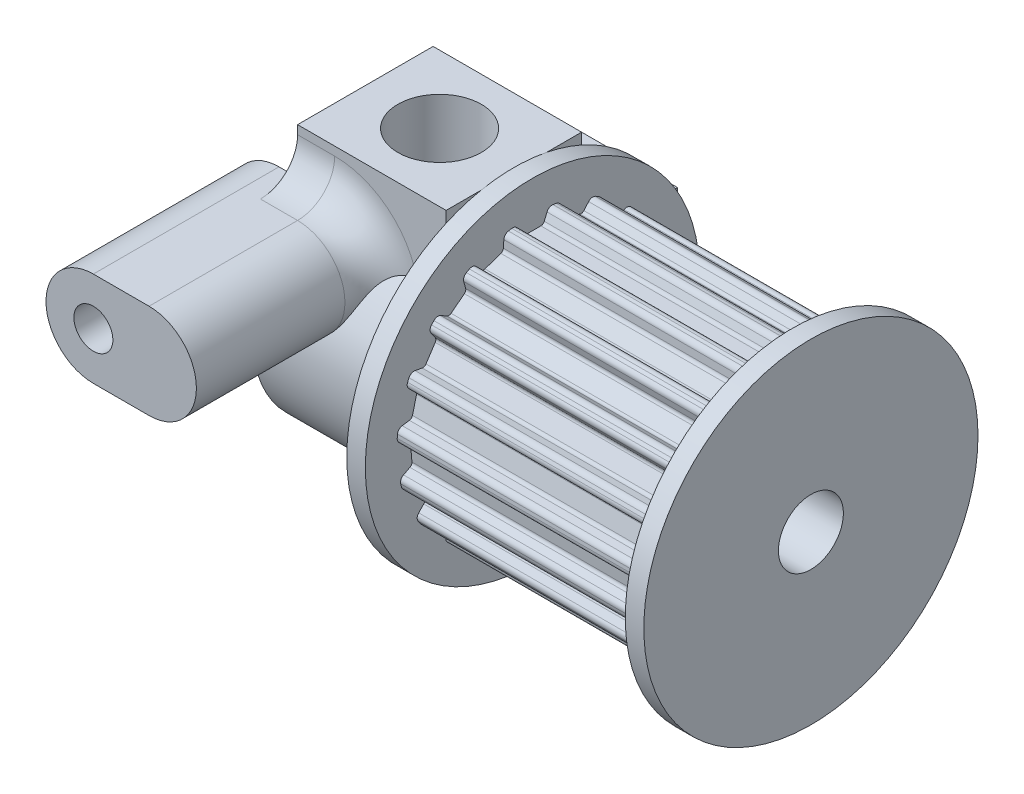
SolidWorks part; units mm, degrees
material "PLA Black"
ref_plane "Front" through (0, 0, 0) normal (0, 0, 1) x (1, 0, 0)
ref_plane "Top" through (0, 0, 0) normal (0, 1, 0) x (1, 0, 0)
ref_plane "Right" through (0, 0, 0) normal (1, 0, 0) x (0, 0, -1)
sketch "Sketch1" plane through (0, 0, 0) normal (1, 0, 0) x (0, 0, -1)
  line L0 (1.118, 1) -> (-1.118, 1) construction
  line L1 (-3.65, 4.8249) -> (3.65, 4.8249)
  line L2 (4.8249, 3.65) -> (4.8249, -3.65)
  line L3 (0, 0) -> (11.6334, 0) construction
  line L4 (0, 0) -> (0, 8.6732) construction
  arc A0 (-1.118, 1) -> (1.118, 1) centre (0, 0) ccw construction
  circle A1 centre (0, 0) radius 1.75
  arc A2 (4.8249, -3.65) -> (-3.65, 4.8249) centre (0, 0) cw
  arc A3 (4.8249, 3.65) -> (3.65, 4.8249) centre (0, 0) ccw
  dimension "D1" = 3
  dimension "D3" = 0.25
  dimension "D5" = 6.05
  dimension "D2" = 1
  dimension "D4" = 7.3
extrude "Boss-Extrude1" add sketch "Sketch1" along normal mid plane 8
sketch "Sketch2" plane through (0, 4.8249, 0) normal (0, 1, 0) x (1, 0, 0)
  circle A0 centre (0, 0) radius 2.25
  dimension "D1" = 4.5
extrude "Cut-Extrude1" cut sketch "Sketch2" against normal blind 5
sketch "Sketch7" plane through (4, 0, 0) normal (1, 0, 0) x (0, 0, -1)
  circle A0 centre (0, 0) radius 1.75 construction
  circle A1 centre (0, 0) radius 7.3
  circle A2 centre (0, 0) radius 1.75
  dimension "D1" = 14.6
extrude "Boss-Extrude5" add sketch "Sketch7" along normal blind 15
sketch "Sketch8" plane through (19, 0, 0) normal (1, 0, 0) x (0, 0, -1)
  line L0 (-0.4541, 6.5499) -> (0.4528, 6.5499)
  line L1 (0.6374, 6.6734) -> (0.7865, 7.0333)
  line L2 (-0.6389, 6.6734) -> (-0.788, 7.0333)
  line L6 (0, 9.2013) -> (0, 0) construction
  arc A0 (0.4528, 6.5499) -> (0.6374, 6.6734) centre (0.4526, 6.7499) ccw
  arc A1 (-0.4541, 6.5499) -> (-0.6389, 6.6734) centre (-0.4541, 6.7499) cw
  arc A2 (0.7865, 7.0333) -> (1.1093, 7.2152) centre (1.0638, 6.9187) cw
  arc A3 (-0.788, 7.0333) -> (-1.1108, 7.215) centre (-1.0652, 6.9185) ccw
  circle A4 centre (0, 0) radius 7.3 construction
  arc A5 (-1.1108, 7.215) -> (1.1093, 7.2152) centre (0, 0) cw
  point P3 (-0.0007, 6.5499)
  point P15 (0, 9.84)
extrude "Cut-Extrude3" cut sketch "Sketch8" against normal up to surface (15 mm away) up to face at (4, 0, -7.3)
pattern_circular "CirPattern1" count 19 over 360 about axis through (19, 0, 0) along (-1, 0, 0) of "Cut-Extrude3"
sketch "Sketch9" plane through (19, 0, 0) normal (1, 0, 0) x (0, 0, -1)
  circle A0 centre (0, 0) radius 9
  circle A1 centre (0, 0) radius 1.75 construction
  circle A2 centre (0, 0) radius 1.75
  dimension "D1" = 18
extrude "Boss-Extrude6" add sketch "Sketch9" along normal blind 1
sketch "Sketch10" plane through (4, 0, 0) normal (-1, 0, 0) x (0, 0, 1)
  circle A0 centre (0, 0) radius 9
  circle A1 centre (0, 0) radius 9 construction
  circle A2 centre (0, 0) radius 1.75 construction
  circle A3 centre (0, 0) radius 1.75
extrude "Boss-Extrude7" add sketch "Sketch10" against normal blind 1
sketch "Sketch3" plane through (0, 0, -4.8249) normal (0, 0, -1) x (-1, 0, 0)
  circle A0 centre (0, 0) radius 2.25
  dimension "D1" = 4.5
extrude "Cut-Extrude2" cut sketch "Sketch3" against normal blind 5
sketch "Sketch4" plane through (0, 4.8249, 0) normal (0, 1, 0) x (1, 0, 0)
  line L0 (4, 3.65) -> (-4, 3.65) construction
  line L2 (4, -3.65) -> (-4, -3.65) construction
  line L3 (-4, 3.65) -> (-4, -3.65) construction
  line L4 (4, 3.65) -> (-4, 3.65)
  line L5 (4, 3.65) -> (4, -3.65)
  line L6 (4, -3.65) -> (-4, -3.65)
  line L7 (-4, 3.65) -> (-4, -3.65)
  line L8 (4, 7.3) -> (4, -7.3) construction
  circle A0 centre (0, 0) radius 2.25 construction
  circle A1 centre (0, 0) radius 2.25
extrude "Boss-Extrude2" add sketch "Sketch4" along normal blind 4
sketch "Sketch5" plane through (0, 0, -4.8249) normal (0, 0, -1) x (-1, 0, 0)
  line L0 (-4, 3.65) -> (4, 3.65) construction
  line L1 (4, -3.65) -> (4, 3.65) construction
  line L2 (-4, -3.65) -> (4, -3.65) construction
  line L4 (-4, 3.65) -> (4, 3.65)
  line L5 (4, -3.65) -> (4, 3.65)
  line L6 (-4, -3.65) -> (4, -3.65)
  line L7 (-4, -3.65) -> (-4, 3.65)
  line L8 (-4, -7.3) -> (-4, 7.3) construction
  circle A0 centre (0, 0) radius 2.25 construction
  circle A1 centre (0, 0) radius 2.25
extrude "Boss-Extrude3" add sketch "Sketch5" along normal blind 4
ref_axis "Axis1" through (20, 0, 0) along (-1, 0, 0)
sketch "Sketch6" plane through (0, 0, 3.65) normal (0, 0, 1) x (1, 0, 0)
  line L0 (-4, 8.8249) -> (-4, 4.8249) construction
  line L2 (-2, 6.3555) -> (-5, 6.3555)
  line L3 (-5, 1.2545) -> (-2, 1.2545)
  line L6 (20, 0) -> (-4, 0) construction
  circle A0 centre (-5, 3.805) radius 1.0505
  arc A1 (-5, 6.3555) -> (-5, 1.2545) centre (-5, 3.805) ccw
  arc A2 (-2, 6.3555) -> (-2, 1.2545) centre (-2, 3.805) cw
  dimension "D1" = 2.101
  dimension "D2" = 3.805
  dimension "D3" = 1.5
  dimension "D4" = 1
  dimension "D5" = 3
extrude "Boss-Extrude4" add sketch "Sketch6" along normal blind 10
fillet "Fillet1" radius 2 2 edges at (-0.6029, 5.9388, 3.65) (-3, 6.3555, 3.65)
equation "\"knee_angle\"= 70"
equation "\"ankle_angle\" = 70"
equation "\"hip_angle\" = 30"
equation "\"spring_ankle_parallel_arm_diameter\"= 1.5"
equation "\"spring_ankle_parallel_arm_length\"= 13"
equation "\"spring_ankle_parallel_intern_diameter\"= 5.7"
equation "\"spring_ankle_parallel_angle\"= \"ankle_angle\""
equation "\"spring_ankle_parallel_turns\"= 3"
equation "\"spring_ankle_parallel_pitch\"= \"spring_ankle_parallel_arm_diameter\" * 1.01"
equation "\"spring_ankle_parallel_cutting_distance\"= (1-\"spring_ankle_parallel_angle\" / 360) * \"spring_ankle_parallel_pitch\""
equation "\"spring_ankle_serial_arm_diameter\"= 1.91"
equation "\"spring_ankle_serial_arm_length\"= 10"
equation "\"spring_ankle_serial_intern_diameter\"= 5.7"
equation "\"spring_ankle_serial_angle\"= \"90\""
equation "\"spring_ankle_serial_turns\"= 3"
equation "\"spring_ankle_serial_pitch\"= \"spring_ankle_serial_arm_diameter\" * 1.01"
equation "\"spring_ankle_serial_cutting_distance\"= (1-\"spring_ankle_serial_angle\" / 360) * \"spring_ankle_serial_pitch\""
equation "\"spring_knee_parallel_arm_diameter\"= 1.5"
equation "\"spring_knee_parallel_arm_length\"= 13"
equation "\"spring_knee_parallel_intern_diameter\"= 5.7"
equation "\"spring_knee_parallel_angle\"= -\"knee_angle\" + 90"
equation "\"spring_knee_parallel_turns\"= 3"
equation "\"spring_knee_parallel_pitch\"= \"spring_knee_parallel_arm_diameter\" * 1.01"
equation "\"spring_knee_parallel_cutting_distance\"= (1-(\"spring_knee_parallel_angle\") / 360) * \"spring_knee_parallel_pitch\""
equation "\"spring_knee_serial_arm_diameter\"= 1.91"
equation "\"spring_knee_serial_arm_length\"= 10"
equation "\"spring_knee_serial_intern_diameter\"= 5.7"
equation "\"spring_knee_serial_angle\"= \"90\""
equation "\"spring_knee_serial_turns\"= 3"
equation "\"spring_knee_serial_pitch\"= \"spring_knee_serial_arm_diameter\" * 1.01"
equation "\"spring_knee_serial_cutting_distance\"= (1-\"spring_knee_serial_angle\" / 360) * \"spring_knee_serial_pitch\""
equation "\"D2@Sketch6\" = ( \"spring_knee_serial_intern_diameter\" + \"spring_knee_serial_arm_diameter\" ) / 2"
equation "\"D1@Sketch6\"=\"spring_knee_serial_arm_diameter\"*1.1"
